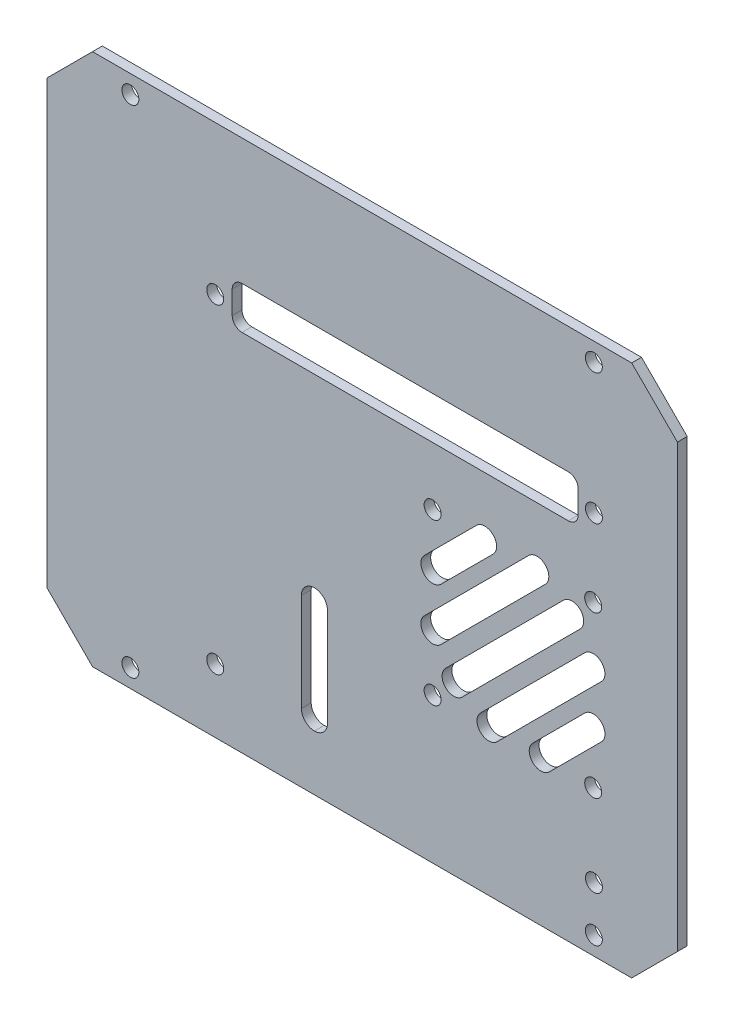
SolidWorks part; units mm, degrees
ref_plane "前视基准面" through (0, 0, 0) normal (0, 0, 1) x (1, 0, 0)
ref_plane "上视基准面" through (0, 0, 0) normal (0, 1, 0) x (1, 0, 0)
ref_plane "右视基准面" through (0, 0, 0) normal (1, 0, 0) x (0, 0, -1)
sketch "草图2" plane through (0, 0, -39.19) normal (0, 0, -1) x (-1, 0, 0)
  line L32 (-47.3467, -34.0538) -> (-40.3426, -41.058)
  line L33 (-40.3426, -41.058) -> (42.2491, -41.058)
  line L34 (42.2491, -41.058) -> (49.2533, -34.0538)
  line L35 (49.2533, -34.0538) -> (49.2533, 33.5378)
  line L36 (49.2533, 33.5378) -> (42.2491, 40.542)
  line L37 (-47.3467, 33.5378) -> (-47.3467, -34.0538)
  line L38 (-40.3426, 40.542) -> (-47.3467, 33.5378)
  line L39 (42.2491, 40.542) -> (-40.3426, 40.542)
  line L40 (-47.3467, -34.0538) -> (-40.3426, -41.058)
  line L41 (-40.3426, -41.058) -> (42.2491, -41.058)
  line L42 (42.2491, -41.058) -> (49.2533, -34.0538)
  line L43 (49.2533, -34.0538) -> (49.2533, 33.5378)
  line L44 (49.2533, 33.5378) -> (42.2491, 40.542)
  line L45 (-47.3467, 33.5378) -> (-47.3467, -34.0538)
  line L46 (-40.3426, 40.542) -> (-47.3467, 33.5378)
  line L47 (42.2491, 40.542) -> (-40.3426, 40.542)
  dimension "D1" = 0.2
extrude "凸台-拉伸1" add sketch "草图2" along normal blind 1.5
sketch "草图3" plane through (0, 0, -40.69) normal (0, 0, -1) x (-1, 0, 0)
  circle A0 centre (-34.5467, -38.258) radius 1.3
  circle A1 centre (36.4533, -38.258) radius 1.3
  circle A2 centre (-34.5467, 37.742) radius 1.3
  circle A3 centre (36.4533, 37.742) radius 1.3
  dimension "D1" = 2.6
extrude "切除-拉伸1" cut sketch "草图3" against normal through all
sketch "草图4" plane through (0, 0, -40.69) normal (0, 0, -1) x (-1, 0, 0)
  circle A1 centre (23.4533, -31.2932) radius 1.3
  circle A2 centre (23.4533, -31.2932) radius 1.3
  circle A3 centre (-34.5583, -31.2932) radius 1.3
  circle A4 centre (-34.5583, -31.2932) radius 1.3
  circle A5 centre (23.4533, 17.742) radius 1.3
  circle A6 centre (23.4533, 17.742) radius 1.3
  circle A7 centre (-34.5583, 17.742) radius 1.3
  circle A8 centre (-34.5583, 17.742) radius 1.3
  dimension "D1" = 0
  dimension "D2" = 0
  dimension "D3" = 0
  dimension "D4" = 0
extrude "切除-拉伸2" cut sketch "草图4" against normal up to next
sketch "草图5" plane through (0, 0, -40.69) normal (0, 0, -1) x (-1, 0, 0)
  line L1 (-32.1467, 14.742) -> (20.8533, 14.742)
  line L2 (-32.1467, 14.742) -> (-32.1467, 21.242)
  line L3 (-32.1467, 21.242) -> (20.8533, 21.242)
  line L4 (20.8533, 14.742) -> (20.8533, 21.242)
  line L7 (-47.3467, 33.5378) -> (-47.3467, -34.0538) construction
  line L9 (42.2491, 40.542) -> (-40.3426, 40.542) construction
  dimension "D1" = 53
  dimension "D2" = 6.5
  dimension "D3" = 15.2
  dimension "D4" = 19.3
extrude "切除-拉伸3" cut sketch "草图5" against normal up to next
fillet "圆角1" radius 1.5 4 edges at (32.1467, 21.242, -39.94) (32.1467, 14.742, -39.94) (-20.8533, 14.742, -39.94) (-20.8533, 21.242, -39.94)
sketch "草图7" plane through (0, 0, -40.69) normal (0, 0, -1) x (-1, 0, 0)
  circle A0 centre (-34.4467, 5.842) radius 1.3
  circle A1 centre (-34.4467, -18.758) radius 1.3
  circle A2 centre (-9.8467, 5.842) radius 1.3
  circle A3 centre (-9.8467, -18.758) radius 1.3
  circle A4 centre (-34.5583, 17.742) radius 1.3 construction
extrude "切除-拉伸4" cut sketch "草图7" against normal up to next
sketch "草图8" plane through (0, 0, -40.69) normal (0, 0, -1) x (-1, 0, 0)
  line L0 (-34.4467, 5.842) -> (-9.8467, -18.758) construction
  line L1 (-34.4467, 5.842) -> (-9.8467, 5.842) construction
  line L2 (-34.4467, 5.842) -> (-34.4467, -18.758) construction
  line L3 (-34.4467, -18.758) -> (-9.8467, -18.758) construction
  line L4 (-9.8467, 5.842) -> (-9.8467, -18.758) construction
  line L5 (-31.194, 2.5893) -> (-13.0994, -15.5053) construction
  line L6 (-29.9212, 3.8621) -> (-11.8266, -14.2325)
  line L7 (-32.4668, 1.3165) -> (-14.3722, -16.7781)
  line L8 (-34.4467, -2.758) -> (-18.4467, -18.758) construction
  line L9 (-33.1739, -1.4852) -> (-17.1739, -17.4852)
  line L10 (-35.7195, -4.0308) -> (-19.7195, -20.0308)
  line L11 (-25.8467, 5.842) -> (-9.8467, -10.158) construction
  line L12 (-24.5739, 7.1148) -> (-8.5739, -8.8852)
  line L13 (-27.1195, 4.5692) -> (-11.1195, -11.4308)
  line L14 (-17.8467, 5.842) -> (-9.8467, -2.158) construction
  line L15 (-16.5739, 7.1148) -> (-8.5739, -0.8852)
  line L16 (-19.1195, 4.5692) -> (-11.1195, -3.4308)
  line L17 (-34.4467, -10.758) -> (-26.4467, -18.758) construction
  line L18 (-33.1739, -9.4852) -> (-25.1739, -17.4852)
  line L19 (-35.7195, -12.0308) -> (-27.7195, -20.0308)
  arc A1 (-29.9212, 3.8621) -> (-32.4668, 1.3165) centre (-31.194, 2.5893) ccw
  arc A2 (-14.3722, -16.7781) -> (-11.8266, -14.2325) centre (-13.0994, -15.5053) ccw
  arc A3 (-33.1739, -1.4852) -> (-35.7195, -4.0308) centre (-34.4467, -2.758) ccw
  arc A4 (-19.7195, -20.0308) -> (-17.1739, -17.4852) centre (-18.4467, -18.758) ccw
  arc A5 (-24.5739, 7.1148) -> (-27.1195, 4.5692) centre (-25.8467, 5.842) ccw
  arc A6 (-11.1195, -11.4308) -> (-8.5739, -8.8852) centre (-9.8467, -10.158) ccw
  arc A7 (-16.5739, 7.1148) -> (-19.1195, 4.5692) centre (-17.8467, 5.842) ccw
  arc A8 (-11.1195, -3.4308) -> (-8.5739, -0.8852) centre (-9.8467, -2.158) ccw
  arc A9 (-33.1739, -9.4852) -> (-35.7195, -12.0308) centre (-34.4467, -10.758) ccw
  arc A10 (-27.7195, -20.0308) -> (-25.1739, -17.4852) centre (-26.4467, -18.758) ccw
  point P10 (-22.1467, -6.458)
  point P15 (-26.4467, -10.758)
  point P22 (-17.8467, -2.158)
  point P29 (-13.8467, 1.842)
  point P36 (-30.4467, -14.758)
  dimension "D1" = 1.8
  dimension "D2" = 1.8
  dimension "D3" = 1.8
  dimension "D4" = 1.8
  dimension "D5" = 1.8
  dimension "D6" = 8
  dimension "D7" = 8
  dimension "D8" = 8
  dimension "D9" = 8
  dimension "D10" = 4.6
  dimension "D11" = 4.6
extrude "切除-拉伸5" cut sketch "草图8" against normal up to next
sketch "草图9" plane through (0, 0, -40.69) normal (0, 0, -1) x (-1, 0, 0)
  line L0 (49.2533, -34.0538) -> (49.2533, 33.5378) construction
  line L1 (6.2533, -13.5932) -> (10.2533, -13.5932)
  line L2 (6.2533, -13.5932) -> (6.2533, -32.5932)
  line L3 (6.2533, -32.5932) -> (10.2533, -32.5932)
  line L4 (10.2533, -13.5932) -> (10.2533, -32.5932)
  circle A1 centre (23.4533, -31.2932) radius 1.3 construction
  dimension "D1" = 39
  dimension "D2" = 4
  dimension "D3" = 19
extrude "切除-拉伸6" cut sketch "草图9" against normal blind 8
fillet "圆角2" radius 2 4 edges at (-6.2533, -32.5932, -39.94) (-10.2533, -32.5932, -39.94) (-10.2533, -13.5932, -39.94) (-6.2533, -13.5932, -39.94)
